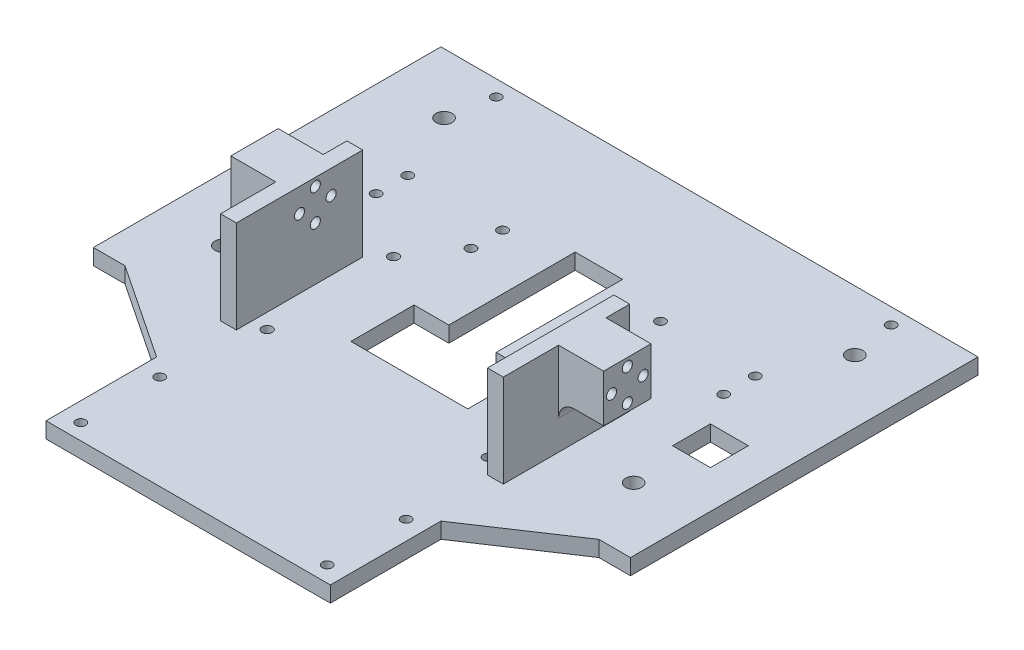
SolidWorks part; units mm, degrees
ref_plane "Front Plane" through (0, 0, 0) normal (0, 0, 1) x (1, 0, 0)
ref_plane "Top Plane" through (0, 0, 0) normal (0, 1, 0) x (1, 0, 0)
ref_plane "Right Plane" through (0, 0, 0) normal (1, 0, 0) x (0, 0, -1)
sketch "Sketch1" plane through (0, 0, 0) normal (0, 1, 0) x (1, 0, 0)
  line L1 (-75, 85) -> (75, 85)
  line L2 (-75, 85) -> (-75, -85)
  line L3 (-75, -85) -> (75, -85)
  line L4 (75, 85) -> (75, -85)
  line L5 (-75, 85) -> (75, -85) construction
  line L6 (-75, -85) -> (75, 85) construction
  line L7 (45, -85) -> (-45, -85)
  line L8 (45, -85) -> (45, -80)
  line L9 (45, -80) -> (-45, -80)
  line L10 (-45, -85) -> (-45, -80)
  line L11 (-18.5, 10) -> (18.5, 10)
  line L12 (-18.5, 10) -> (-18.5, -10)
  line L13 (-18.5, -10) -> (18.5, -10)
  line L14 (18.5, 10) -> (18.5, -10)
  line L15 (-18.5, 10) -> (18.5, -10) construction
  line L16 (-18.5, -10) -> (18.5, 10) construction
  line L17 (45, -85) -> (75, -85)
  line L18 (45, -85) -> (45, -45)
  line L19 (45, -45) -> (75, -45)
  line L20 (75, -85) -> (75, -45)
  line L21 (-45, -85) -> (-75, -85)
  line L22 (-45, -85) -> (-45, -45)
  line L23 (-45, -45) -> (-75, -45)
  line L24 (-75, -85) -> (-75, -45)
  line L25 (75, -25) -> (75, -45)
  line L26 (-7.5, 10) -> (7.5, 10)
  line L27 (45, -45) -> (75, -25)
  line L28 (-45, -45) -> (-75, -25)
  line L29 (-7.5, 10) -> (-7.5, 50)
  line L30 (-7.5, 50) -> (7.5, 50)
  line L31 (7.5, 10) -> (7.5, 50)
  point P0 (0, 0)
  point P10 (0, 0)
  dimension "D1" = 150
  dimension "D2" = 170
  dimension "D3" = 30
  dimension "D4" = 30
  dimension "D5" = 5
  dimension "D6" = 37
  dimension "D7" = 20
  dimension "D8" = 40
  dimension "D9" = 40
  dimension "D10" = 20
  dimension "D11" = 20
  dimension "D12" = 7.5
  dimension "D13" = 7.5
  dimension "D14" = 40
extrude "Boss-Extrude1" add sketch "Sketch1" along normal blind 5 contours L23 L22 L9 L18 L19 L4 L1 L2 L11 L14 L13 L12 region at (0, 0, -82.7701)
sketch "Sketch2" plane through (0, 5, 0) normal (0, 1, 0) x (1, 0, 0)
  line L0 (0, 0) -> (0, -39.6646) construction
sketch "Sketch3" plane through (0, 5, 0) normal (0, 1, 0) x (1, 0, 0)
  line L0 (-18.5, 10) -> (-18.5, -10) construction
  line L1 (-18.5, 10) -> (-7.5, 10) construction
  line L2 (0, 0) -> (0, -17.2633) construction
  circle A0 centre (-35, 20) radius 1.6
  circle A1 centre (-35, -20) radius 1.6
  circle A2 centre (35, -20) radius 1.6
  circle A3 centre (35, 20) radius 1.6
  dimension "D1" = 3.2
  dimension "D2" = 40
  dimension "D3" = 16.5
  dimension "D4" = 10
extrude "Cut-Extrude1" cut sketch "Sketch3" against normal through all and the other way through all
sketch "Sketch4" plane through (0, 5, 0) normal (0, 1, 0) x (1, 0, 0)
  line L0 (-75, 85) -> (75, 85) construction
  line L1 (-75, 85) -> (-70, 85)
  line L2 (-75, 85) -> (-75, -23)
  line L3 (-75, -23) -> (-70, -23)
  line L4 (-70, 85) -> (-70, -23)
  line L5 (-70, -11.5) -> (-75, -11.5)
  line L6 (-70, -11.5) -> (-70, 3.5)
  line L7 (-70, 3.5) -> (-75, 3.5)
  line L8 (-75, -11.5) -> (-75, 3.5)
  line L9 (-70, 23.5) -> (-75, 23.5)
  line L10 (-70, 23.5) -> (-70, 38.5)
  line L11 (-70, 38.5) -> (-75, 38.5)
  line L12 (-75, 23.5) -> (-75, 38.5)
  line L13 (0, 0) -> (0, 26.7337) construction
  line L14 (-70, 3.5) -> (-60, 3.5)
  line L15 (-70, 58.5) -> (-75, 58.5)
  line L16 (-70, 58.5) -> (-70, 73.5)
  line L17 (-70, 73.5) -> (-75, 73.5)
  line L18 (-75, 58.5) -> (-75, 73.5)
  line L19 (-70, 73.5) -> (-60, 73.5)
  line L20 (-70, 73.5) -> (-70, 58.5)
  line L21 (-70, 58.5) -> (-60, 58.5)
  line L22 (-60, 73.5) -> (-60, 58.5)
  line L23 (-70, 3.5) -> (-70, -11.5)
  line L24 (-70, -11.5) -> (-60, -11.5)
  line L25 (-60, 3.5) -> (-60, -11.5)
  circle A0 centre (-65, 66) radius 2.55
  circle A1 centre (-65, -4) radius 2.55
  circle A2 centre (65, 66) radius 2.55
  circle A3 centre (65, -4) radius 2.55
  dimension "D10" = 5.1
  dimension "D12" = 5.1
  dimension "D13" = 7.5
  dimension "D14" = 5
  dimension "D15" = 5
  dimension "D16" = 7.5
  dimension "D1" = 5
  dimension "D2" = 15
  dimension "D3" = 108
  dimension "D4" = 15
  dimension "D5" = 20
  dimension "D6" = 15
  dimension "D7" = 20
  dimension "D8" = 11.5
  dimension "D9" = 10
  dimension "D11" = 10
extrude "Cut-Extrude2" cut sketch "Sketch4" against normal blind 10 contours A0 | A3 | A1 | A2 region at (-65, 5, -66) region at (65, 5, 4)
sketch "Sketch5" plane through (0, 5, 0) normal (0, 1, 0) x (1, 0, 0)
  line L0 (0, 0) -> (0, -51.3371) construction
  line L1 (45, -80) -> (-45, -80) construction
  line L4 (-45, -45) -> (-42, -45)
  line L5 (-45, -45) -> (-45, -80)
  line L6 (-45, -80) -> (-42, -80)
  line L7 (-42, -45) -> (-42, -80)
  line L8 (-42, -70) -> (-36, -70)
  line L9 (-42, -70) -> (-42, -80)
  line L10 (-42, -80) -> (-36, -80)
  line L11 (-36, -70) -> (-36, -80)
  circle A0 centre (-39, -75) radius 1.55
  circle A1 centre (39, -75) radius 1.55
  circle A2 centre (-39, -50) radius 1.55
  circle A3 centre (39, -50) radius 1.55
  dimension "D1" = 3.1
  dimension "D2" = 5
  dimension "D3" = 3
  dimension "D8" = 3.1
  dimension "D9" = 25
  dimension "D10" = 5
  dimension "D4" = 3
  dimension "D5" = 6
  dimension "D6" = 0
  dimension "D7" = 10
extrude "Cut-Extrude3" cut sketch "Sketch5" against normal through all contours A2 | A0 | A1 | A3
sketch "Sketch6" plane through (0, 5, 0) normal (0, 1, 0) x (1, 0, 0)
  line L0 (-75, 85) -> (75, 85) construction
  line L1 (70, 85) -> (55, 85)
  line L2 (70, 85) -> (70, 75)
  line L3 (70, 75) -> (55, 75)
  line L4 (55, 85) -> (55, 75)
  line L5 (75, 85) -> (75, -25) construction
  line L6 (0, 0) -> (0, 22.1653) construction
  line L7 (-55, 85) -> (-55, 75)
  line L8 (-70, 75) -> (-55, 75)
  line L9 (-70, 85) -> (-70, 75)
  line L10 (-70, 85) -> (-55, 85)
  circle A0 centre (62.5, 80) radius 1.55
  circle A1 centre (-62.5, 80) radius 1.55
  dimension "D4" = 3.1
  dimension "D5" = 5
  dimension "D6" = 7.5
  dimension "D1" = 5
  dimension "D2" = 10
  dimension "D3" = 15
extrude "Cut-Extrude4" cut sketch "Sketch6" against normal through all contours A0 | A1 region at (62.5, 5, -80)
sketch "Sketch7" plane through (0, 5, 0) normal (0, 1, 0) x (1, 0, 0)
  line L0 (0, 0) -> (0, 72.5289) construction
  line L1 (-75, 85) -> (-98, 85)
  line L2 (-75, 85) -> (-75, -25)
  line L3 (-75, -25) -> (-98, -25)
  line L4 (-98, 85) -> (-98, -25)
  line L5 (98, 85) -> (98, -25)
  line L6 (75, -25) -> (98, -25)
  line L7 (75, 85) -> (75, -25)
  line L8 (75, 85) -> (98, 85)
  dimension "D1" = 23
extrude "Boss-Extrude2" add sketch "Sketch7" against normal blind 5
sketch "Sketch9" plane through (0, 5, 0) normal (0, 1, 0) x (1, 0, 0)
  line L1 (-44.75, 15) -> (-39.75, 15)
  line L2 (-44.75, 15) -> (-44.75, -25)
  line L3 (-44.75, -25) -> (-39.75, -25)
  line L4 (-39.75, 15) -> (-39.75, -25)
  line L8 (0, 0) -> (0, -58.9253) construction
  line L9 (39.75, 15) -> (39.75, -25)
  line L10 (44.75, -25) -> (39.75, -25)
  line L11 (44.75, 15) -> (44.75, -25)
  line L12 (44.75, 15) -> (39.75, 15)
  line L14 (-98, 85) -> (-98, -25) construction
  dimension "D1" = 53.25
  dimension "D2" = 5
  dimension "D3" = 40
extrude "Boss-Extrude4" add sketch "Sketch9" along normal blind 33
sketch "Sketch11" plane through (0, 5, 0) normal (0, 1, 0) x (1, 0, 0)
  line L0 (-98, 85) -> (-98, -25) construction
  line L1 (-73, 24.3058) -> (-61, 24.3058)
  line L2 (-73, 24.3058) -> (-73, 12.3058)
  line L3 (-73, 12.3058) -> (-61, 12.3058)
  line L4 (-61, 24.3058) -> (-61, 12.3058)
  line L5 (0, 0) -> (0, 34.4815) construction
  line L6 (61, 24.3058) -> (61, 12.3058)
  line L7 (73, 12.3058) -> (61, 12.3058)
  line L8 (73, 24.3058) -> (73, 12.3058)
  line L9 (73, 24.3058) -> (61, 24.3058)
  dimension "D1" = 25
  dimension "D2" = 12
  dimension "D3" = 12
extrude "Cut-Extrude5" cut sketch "Sketch11" against normal blind 50
sketch "Sketch12" plane through (-44.75, 0, 0) normal (-1, 0, 0) x (0, 0, 1)
  line L0 (-15, 38) -> (-15, 5) construction
  line L1 (-7.5, 34.35) -> (7.5, 34.35)
  line L2 (-7.5, 34.35) -> (-7.5, 19.35)
  line L3 (-7.5, 19.35) -> (7.5, 19.35)
  line L4 (7.5, 34.35) -> (7.5, 19.35)
  line L5 (-15, 38) -> (25, 38) construction
  line L6 (0, 34.35) -> (0, 19.35) construction
  line L7 (0, 34.35) -> (0, 26.85) construction
  line L8 (0, 34.35) -> (0, 19.35) construction
  line L9 (0, 19.35) -> (0, 26.85) construction
  line L10 (0, 26.85) -> (7.5, 26.85) construction
  circle A0 centre (0, 31.85) radius 1.6
  circle A4 centre (5, 26.85) radius 1.6
  circle A5 centre (0, 21.85) radius 1.6
  circle A6 centre (-5, 26.85) radius 1.6
  point P23 (-2.6824, 31.0425)
  point P24 (0, 26.85)
  dimension "D5" = 3.2
  dimension "D6" = 5
  dimension "D8" = 0
  dimension "D9" = 5
  dimension "D10" = 5
  dimension "D1" = 7.5
  dimension "D2" = 15
  dimension "D3" = 3.65
  dimension "D4" = 15
  dimension "D7" = 4
extrude "Cut-Extrude6" cut sketch "Sketch12" against normal blind 50 contours A0 | A4 | A6 | A5 region at (-44.75, 31.85, 0) region at (-44.75, 26.85, 5) region at (-44.75, 21.85, 0) region at (-44.75, 26.85, -5)
sketch "Sketch13" plane through (-44.75, 0, 0) normal (-1, 0, 0) x (0, 0, 1)
  line L6 (0, 34.35) -> (0, 19.35) construction
  line L7 (0, 19.35) -> (0, 26.85) construction
  line L8 (0, 26.85) -> (7.5, 26.85) construction
  line L9 (-15, 38) -> (-15, 5) construction
  line L10 (-7.5, 34.35) -> (7.5, 34.35)
  line L11 (-7.5, 34.35) -> (-7.5, 19.35)
  line L12 (-7.5, 19.35) -> (7.5, 19.35)
  line L13 (7.5, 34.35) -> (7.5, 19.35)
  line L14 (-7.5, 34.35) -> (7.5, 19.35) construction
  line L15 (-7.5, 19.35) -> (7.5, 34.35) construction
  circle A2 centre (0, 31.85) radius 1.6
  circle A3 centre (5, 26.85) radius 1.6
  circle A5 centre (-5, 26.85) radius 1.6
  circle A6 centre (0, 21.85) radius 1.6
  dimension "D3" = 5
  dimension "D1" = 7.5
  dimension "D2" = 15
extrude "Boss-Extrude5" add sketch "Sketch13" along normal blind 14.25
ref_plane "Plane2" through (0, 0, 0) normal (-1, 0, 0) x (0, 0, 1)
mirror "Mirror2" about plane through (0, 0, 0) normal (-1, 0, 0) of "Cut-Extrude6"
mirror "Mirror3" about plane through (0, 0, 0) normal (-1, 0, 0) of "Boss-Extrude5"
sketch "Sketch15" plane through (0, 0, 25) normal (0, 0, 1) x (1, 0, 0)
  line L0 (44.75, 19.35) -> (44.75, 34.35) construction
  line L1 (-44.75, 38) -> (44.75, 38)
  line L2 (-44.75, 38) -> (-44.75, 34.35)
  line L3 (-44.75, 34.35) -> (44.75, 34.35)
  line L4 (44.75, 38) -> (44.75, 34.35)
  line L5 (59, 34.35) -> (44.75, 34.35) construction
extrude "Cut-Extrude9" cut sketch "Sketch15" against normal through all
sketch "Sketch18" plane through (0, 5, 0) normal (0, 1, 0) x (1, 0, 0)
  line L0 (-98, -25) -> (-75, -25) construction
  line L1 (-98, 85) -> (-85, 85)
  line L2 (-98, 85) -> (-98, -25)
  line L3 (-98, -25) -> (-85, -25)
  line L4 (-85, 85) -> (-85, -25)
  line L5 (0, 28.0113) -> (0, -28.0113) construction
  line L6 (85, 85) -> (85, -25)
  line L7 (98, -25) -> (85, -25)
  line L8 (98, 85) -> (98, -25)
  line L9 (98, 85) -> (85, 85)
  dimension "D1" = 13
extrude "Cut-Extrude10" cut sketch "Sketch18" against normal through all
fillet "Fillet5" radius 5 2 edges at (44.75, 19.35, 0) (-44.75, 19.35, 0)
sketch "Sketch19" plane through (0, 5, 0) normal (0, 1, 0) x (1, 0, 0)
  line L0 (59, 0) -> (85, 0) construction
  line L1 (59, -7.5) -> (59, 7.5) construction
  line L2 (85, 85) -> (85, -25) construction
  line L3 (85, 0) -> (85, 13) construction
  line L4 (85, 13) -> (85, 78.55) construction
  line L5 (85, 54.5) -> (5, 54.5) construction
  line L6 (5, 54.5) -> (5, 24.5) construction
  line L7 (5, 24.5) -> (85, 24.5) construction
  line L8 (85, 24.5) -> (85, 54.5) construction
  line L9 (85, 54.5) -> (85, 78.5) construction
  circle A0 centre (55, 34.5) radius 1.55
  circle A1 centre (25, 34.5) radius 1.55
  circle A2 centre (25, 44.5) radius 1.55
  circle A3 centre (55, 44.5) radius 1.55
  dimension "D7" = 10
  dimension "3.1" = 3.1
  dimension "D8" = 30
  dimension "D11" = 30
  dimension "D12" = 10
  dimension "D1" = 13
  dimension "D2" = 65.55
  dimension "D3" = 41.5
  dimension "D4" = 80
  dimension "D5" = 30
  dimension "D6" = 24
  dimension "D9" = 2
  dimension "D10" = 2
extrude "Cut-Extrude11" cut sketch "Sketch19" against normal blind 5
mirror "Mirror4" about plane through (0, 0, 0) normal (-1, 0, 0) of "Cut-Extrude11"
sketch "Sketch21" plane through (0, 0, 80) normal (0, 0, 1) x (1, 0, 0)
  line L1 (-85, 0) -> (85, 0)
  line L2 (-85, 0) -> (-85, 5)
  line L3 (-85, 5) -> (85, 5)
  line L4 (85, 0) -> (85, 5)
  line L5 (59, 34.35) -> (39.75, 34.35)
  line L6 (59, 34.35) -> (59, 5)
  line L7 (59, 5) -> (39.75, 5)
  line L8 (39.75, 34.35) -> (39.75, 5)
